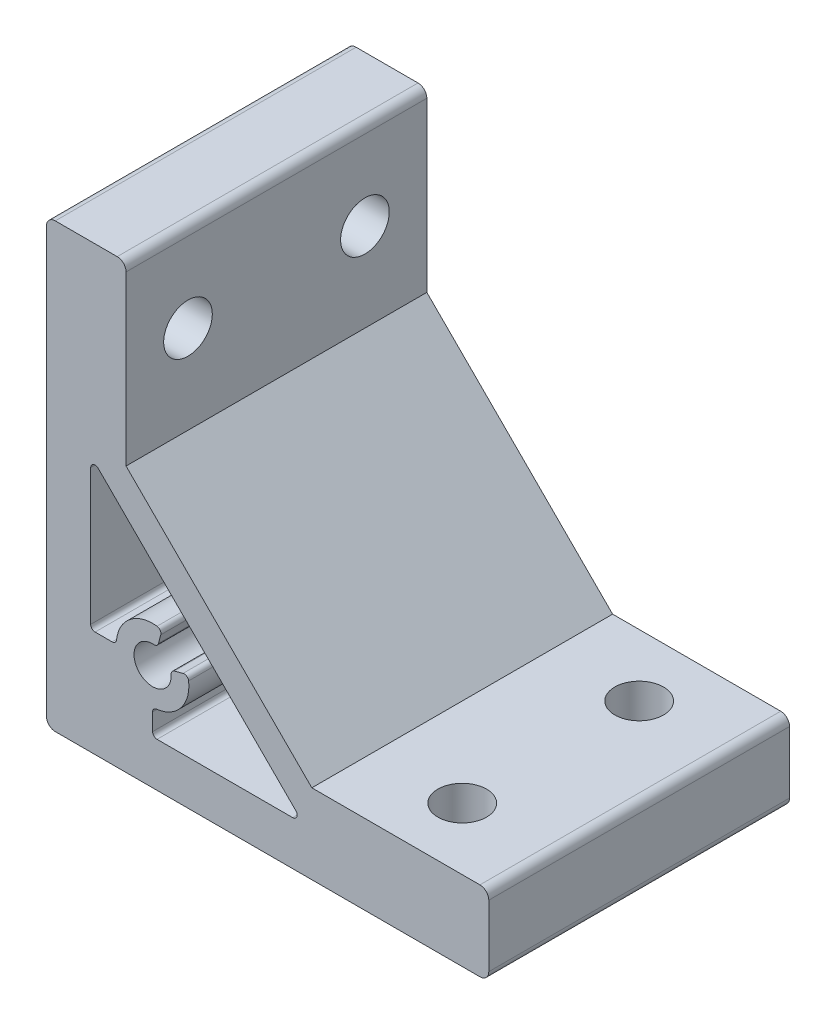
SolidWorks part; units mm, degrees
ref_plane "前视基准面" through (0, 0, 0) normal (0, 0, 1) x (1, 0, 0)
ref_plane "上视基准面" through (0, 0, 0) normal (0, 1, 0) x (1, 0, 0)
ref_plane "右视基准面" through (0, 0, 0) normal (1, 0, 0) x (0, 0, -1)
sketch "草图1" [suppressed] plane through (0, 0, 0) normal (0, 0, 1) x (1, 0, 0)
  line L12 (3, 3) -> (3, 19)
  line L13 (2, 20) -> (1, 20)
  line L14 (0, 19) -> (0, 1)
  line L15 (1, 0) -> (19, 0)
  line L16 (20, 1) -> (20, 2)
  line L17 (19, 3) -> (3, 3)
  arc A10 (3, 19) -> (2, 20) centre (2, 19) ccw
  arc A11 (1, 20) -> (0, 19) centre (1, 19) ccw
  arc A12 (0, 1) -> (1, 0) centre (1, 1) ccw
  arc A13 (19, 0) -> (20, 1) centre (19, 1) ccw
  arc A14 (20, 2) -> (19, 3) centre (19, 2) ccw
extrude "凸台-拉伸1" [suppressed] add sketch "草图1" against normal blind 14
sketch "草图2" [suppressed] plane through (0, 3, 0) normal (0, 1, 0) x (1, 0, 0)
  line L0 (19, 14) -> (3, 14) construction
  line L1 (0, 14) -> (0, 0) construction
  circle A0 centre (14, 7) radius 2.75
  dimension "D1" = 5.5
  dimension "D2" = 7
  dimension "D3" = 14
extrude "切除-拉伸1" [suppressed] cut sketch "草图2" against normal through all
sketch "草图3" [suppressed] plane through (3, 0, 0) normal (1, 0, 0) x (0, 0, -1)
  line L0 (0, 3) -> (0, 19) construction
  line L1 (14, 0) -> (0, 0) construction
  circle A0 centre (7, 14) radius 2.75
  dimension "D1" = 7
  dimension "D2" = 5.5
  dimension "D3" = 14
extrude "切除-拉伸2" [suppressed] cut sketch "草图3" against normal through all
sketch "草图4" [suppressed] plane through (0, 0, 0) normal (0, 0, 1) x (1, 0, 0)
  line L12 (3, 3) -> (3, 19)
  line L13 (2, 20) -> (1, 20)
  line L14 (0, 19) -> (0, 1)
  line L15 (1, 0) -> (19, 0)
  line L16 (20, 1) -> (20, 2)
  line L17 (19, 3) -> (3, 3)
  arc A10 (3, 19) -> (2, 20) centre (2, 19) ccw
  arc A11 (1, 20) -> (0, 19) centre (1, 19) ccw
  arc A12 (0, 1) -> (1, 0) centre (1, 1) ccw
  arc A13 (19, 0) -> (20, 1) centre (19, 1) ccw
  arc A14 (20, 2) -> (19, 3) centre (19, 2) ccw
extrude "凸台-拉伸2" [suppressed] add sketch "草图4" against normal blind 34
sketch "草图5" [suppressed] plane through (0, 3, 0) normal (0, 1, 0) x (1, 0, 0)
  line L0 (20, 17) -> (-10.7961, 17) construction
  line L1 (20, 34) -> (20, 0) construction
  line L2 (0, 34) -> (0, 0) construction
  circle A0 centre (14, 27) radius 2.75
  circle A1 centre (14, 7) radius 2.75
  dimension "D1" = 5.5
  dimension "D2" = 20
  dimension "D3" = 14
extrude "切除-拉伸3" [suppressed] cut sketch "草图5" against normal through all
sketch "草图6" [suppressed] plane through (3, 0, 0) normal (1, 0, 0) x (0, 0, -1)
  line L0 (17, 20) -> (17, -1.671) construction
  line L1 (34, 20) -> (0, 20) construction
  line L2 (34, 0) -> (0, 0) construction
  circle A0 centre (7, 14) radius 2.75
  circle A1 centre (27, 14) radius 2.75
  dimension "D1" = 5.5
  dimension "D2" = 20
  dimension "D3" = 14
extrude "切除-拉伸4" [suppressed] cut sketch "草图6" against normal through all
sketch "草图7" [suppressed] plane through (0, 0, 0) normal (0, 0, 1) x (1, 0, 0)
  line L12 (3, 3) -> (3, 19)
  line L13 (2, 20) -> (1, 20)
  line L14 (0, 19) -> (0, 1)
  line L15 (1, 0) -> (19, 0)
  line L16 (20, 1) -> (20, 2)
  line L17 (19, 3) -> (3, 3)
  arc A10 (3, 19) -> (2, 20) centre (2, 19) ccw
  arc A11 (1, 20) -> (0, 19) centre (1, 19) ccw
  arc A12 (0, 1) -> (1, 0) centre (1, 1) ccw
  arc A13 (19, 0) -> (20, 1) centre (19, 1) ccw
  arc A14 (20, 2) -> (19, 3) centre (19, 2) ccw
extrude "凸台-拉伸3" [suppressed] add sketch "草图7" against normal blind 54
sketch "草图8" [suppressed] plane through (0, 3, 0) normal (0, 1, 0) x (1, 0, 0)
  line L0 (20, 27) -> (-6.5003, 27) construction
  line L1 (20, 54) -> (20, 0) construction
  line L2 (0, 54) -> (0, 0) construction
  circle A0 centre (14, 47) radius 2.75
  circle A1 centre (14, 27) radius 2.75
  circle A2 centre (14, 7) radius 2.75
  dimension "D1" = 5.5
  dimension "D2" = 20
  dimension "D3" = 14
extrude "切除-拉伸5" [suppressed] cut sketch "草图8" against normal through all
sketch "草图9" [suppressed] plane through (3, 0, 0) normal (1, 0, 0) x (0, 0, -1)
  line L0 (27, 20) -> (27, 28.1098) construction
  line L1 (54, 20) -> (0, 20) construction
  line L2 (54, 0) -> (0, 0) construction
  circle A0 centre (7, 14) radius 2.75
  circle A1 centre (27, 14) radius 2.75
  circle A2 centre (47, 14) radius 2.75
  dimension "D1" = 5.5
  dimension "D2" = 20
  dimension "D3" = 14
extrude "切除-拉伸6" [suppressed] cut sketch "草图9" against normal through all
sketch "草图10" [suppressed] plane through (0, 0, 0) normal (0, 0, 1) x (1, 0, 0)
  line L20 (7.8119, 14.1881) -> (5, 17)
  line L21 (5, 17) -> (5, 34)
  line L22 (4, 35) -> (1, 35)
  line L23 (0, 34) -> (0, 1)
  line L24 (1, 0) -> (34, 0)
  line L25 (35, 1) -> (35, 4)
  line L26 (34, 5) -> (17, 5)
  line L27 (17, 5) -> (14.1881, 7.8119)
  line L28 (15.4436, 12.9222) -> (14.4646, 12.6602)
  line L29 (12.6602, 14.4646) -> (12.9222, 15.4436)
  arc A28 (5, 34) -> (4, 35) centre (4, 34) ccw
  arc A29 (1, 35) -> (0, 34) centre (1, 34) ccw
  arc A30 (0, 1) -> (1, 0) centre (1, 1) ccw
  arc A31 (34, 0) -> (35, 1) centre (34, 1) ccw
  arc A32 (35, 4) -> (34, 5) centre (34, 4) ccw
  arc A33 (14.265, 8.582) -> (14.1881, 7.8119) centre (14.5416, 8.1655) ccw
  arc A34 (14.265, 8.582) -> (16.069, 12.501) centre (11.9998, 11.9994) ccw
  arc A35 (16.069, 12.501) -> (15.4436, 12.9222) centre (15.5728, 12.4392) ccw
  arc A36 (14.4646, 12.6602) -> (14.095, 12.143) centre (14.5938, 12.1772) ccw
  arc A37 (12.143, 14.095) -> (14.095, 12.143) centre (11.9999, 11.9999) ccw
  arc A38 (12.143, 14.095) -> (12.6602, 14.4646) centre (12.1772, 14.5938) ccw
  arc A39 (12.9222, 15.4436) -> (12.501, 16.069) centre (12.4392, 15.5728) ccw
  arc A40 (12.501, 16.069) -> (8.582, 14.265) centre (11.9994, 11.9998) ccw
  arc A41 (7.8119, 14.1881) -> (8.582, 14.265) centre (8.1655, 14.5416) ccw
extrude "凸台-拉伸4" [suppressed] add sketch "草图10" against normal blind 14
sketch "草图11" [suppressed] plane through (0, 5, 0) normal (0, 1, 0) x (1, 0, 0)
  line L0 (34, 14) -> (17, 14) construction
  line L1 (0, 14) -> (0, 0) construction
  circle A0 centre (26, 7) radius 2.75
  dimension "D1" = 7
  dimension "D2" = 5.5
  dimension "D3" = 26
extrude "切除-拉伸7" [suppressed] cut sketch "草图11" against normal through all
sketch "草图12" [suppressed] plane through (5, 0, 0) normal (1, 0, 0) x (0, 0, -1)
  line L0 (0, 17) -> (0, 34) construction
  line L1 (14, 0) -> (0, 0) construction
  circle A0 centre (7, 26) radius 2.75
  dimension "D1" = 5.5
  dimension "D2" = 7
  dimension "D3" = 26
extrude "切除-拉伸8" [suppressed] cut sketch "草图12" against normal through all
sketch "草图13" [suppressed] plane through (0, 0, 0) normal (0, 0, 1) x (1, 0, 0)
  line L20 (7.8119, 14.1881) -> (5, 17)
  line L21 (5, 17) -> (5, 34)
  line L22 (4, 35) -> (1, 35)
  line L23 (0, 34) -> (0, 1)
  line L24 (1, 0) -> (34, 0)
  line L25 (35, 1) -> (35, 4)
  line L26 (34, 5) -> (17, 5)
  line L27 (17, 5) -> (14.1881, 7.8119)
  line L28 (15.4436, 12.9222) -> (14.4646, 12.6602)
  line L29 (12.6602, 14.4646) -> (12.9222, 15.4436)
  arc A28 (5, 34) -> (4, 35) centre (4, 34) ccw
  arc A29 (1, 35) -> (0, 34) centre (1, 34) ccw
  arc A30 (0, 1) -> (1, 0) centre (1, 1) ccw
  arc A31 (34, 0) -> (35, 1) centre (34, 1) ccw
  arc A32 (35, 4) -> (34, 5) centre (34, 4) ccw
  arc A33 (14.265, 8.582) -> (14.1881, 7.8119) centre (14.5416, 8.1655) ccw
  arc A34 (14.265, 8.582) -> (16.069, 12.501) centre (11.9998, 11.9994) ccw
  arc A35 (16.069, 12.501) -> (15.4436, 12.9222) centre (15.5728, 12.4392) ccw
  arc A36 (14.4646, 12.6602) -> (14.095, 12.143) centre (14.5938, 12.1772) ccw
  arc A37 (12.143, 14.095) -> (14.095, 12.143) centre (11.9999, 11.9999) ccw
  arc A38 (12.143, 14.095) -> (12.6602, 14.4646) centre (12.1772, 14.5938) ccw
  arc A39 (12.9222, 15.4436) -> (12.501, 16.069) centre (12.4392, 15.5728) ccw
  arc A40 (12.501, 16.069) -> (8.582, 14.265) centre (11.9994, 11.9998) ccw
  arc A41 (7.8119, 14.1881) -> (8.582, 14.265) centre (8.1655, 14.5416) ccw
extrude "凸台-拉伸5" [suppressed] add sketch "草图13" against normal blind 34
sketch "草图14" [suppressed] plane through (0, 5, 0) normal (0, 1, 0) x (1, 0, 0)
  line L0 (35, 17) -> (-9.0369, 17) construction
  line L1 (35, 34) -> (35, 0) construction
  line L2 (0, 34) -> (0, 0) construction
  circle A0 centre (26, 27) radius 2.75
  circle A1 centre (26, 7) radius 2.75
  dimension "D1" = 5.5
  dimension "D2" = 20
  dimension "D3" = 26
extrude "切除-拉伸9" [suppressed] cut sketch "草图14" against normal through all
sketch "草图15" [suppressed] plane through (5, 0, 0) normal (1, 0, 0) x (0, 0, -1)
  line L0 (17, 35) -> (17, -2.0911) construction
  line L1 (34, 35) -> (0, 35) construction
  line L2 (34, 0) -> (0, 0) construction
  circle A0 centre (7, 26) radius 2.75
  circle A1 centre (27, 26) radius 2.75
  dimension "D1" = 5.5
  dimension "D2" = 20
  dimension "D3" = 26
extrude "切除-拉伸10" [suppressed] cut sketch "草图15" against normal through all
sketch "草图16" [suppressed] plane through (0, 0, 0) normal (0, 0, 1) x (1, 0, 0)
  line L20 (7.8119, 14.1881) -> (5, 17)
  line L21 (5, 17) -> (5, 34)
  line L22 (4, 35) -> (1, 35)
  line L23 (0, 34) -> (0, 1)
  line L24 (1, 0) -> (34, 0)
  line L25 (35, 1) -> (35, 4)
  line L26 (34, 5) -> (17, 5)
  line L27 (17, 5) -> (14.1881, 7.8119)
  line L28 (15.4436, 12.9222) -> (14.4646, 12.6602)
  line L29 (12.6602, 14.4646) -> (12.9222, 15.4436)
  arc A28 (5, 34) -> (4, 35) centre (4, 34) ccw
  arc A29 (1, 35) -> (0, 34) centre (1, 34) ccw
  arc A30 (0, 1) -> (1, 0) centre (1, 1) ccw
  arc A31 (34, 0) -> (35, 1) centre (34, 1) ccw
  arc A32 (35, 4) -> (34, 5) centre (34, 4) ccw
  arc A33 (14.265, 8.582) -> (14.1881, 7.8119) centre (14.5416, 8.1655) ccw
  arc A34 (14.265, 8.582) -> (16.069, 12.501) centre (11.9998, 11.9994) ccw
  arc A35 (16.069, 12.501) -> (15.4436, 12.9222) centre (15.5728, 12.4392) ccw
  arc A36 (14.4646, 12.6602) -> (14.095, 12.143) centre (14.5938, 12.1772) ccw
  arc A37 (12.143, 14.095) -> (14.095, 12.143) centre (11.9999, 11.9999) ccw
  arc A38 (12.143, 14.095) -> (12.6602, 14.4646) centre (12.1772, 14.5938) ccw
  arc A39 (12.9222, 15.4436) -> (12.501, 16.069) centre (12.4392, 15.5728) ccw
  arc A40 (12.501, 16.069) -> (8.582, 14.265) centre (11.9994, 11.9998) ccw
  arc A41 (7.8119, 14.1881) -> (8.582, 14.265) centre (8.1655, 14.5416) ccw
extrude "凸台-拉伸6" [suppressed] add sketch "草图16" against normal blind 54
sketch "草图17" [suppressed] plane through (0, 5, 0) normal (0, 1, 0) x (1, 0, 0)
  line L0 (35, 27) -> (46.9961, 27) construction
  line L1 (35, 54) -> (35, 0) construction
  line L2 (0, 54) -> (0, 0) construction
  circle A0 centre (26, 47) radius 2.75
  circle A1 centre (26, 27) radius 2.75
  circle A2 centre (26, 7) radius 2.75
  dimension "D1" = 5.5
  dimension "D2" = 20
  dimension "D3" = 26
extrude "切除-拉伸11" [suppressed] cut sketch "草图17" against normal through all
sketch "草图18" [suppressed] plane through (5, 0, 0) normal (1, 0, 0) x (0, 0, -1)
  line L0 (27, 35) -> (27, 41.3305) construction
  line L1 (54, 35) -> (0, 35) construction
  line L2 (54, 0) -> (0, 0) construction
  circle A0 centre (7, 26) radius 2.75
  circle A1 centre (27, 26) radius 2.75
  circle A2 centre (47, 26) radius 2.75
  dimension "D1" = 5.5
  dimension "D2" = 20
  dimension "D3" = 26
extrude "切除-拉伸12" [suppressed] cut sketch "草图18" against normal through all
sketch "草图19" [suppressed] plane through (0, 0, 0) normal (0, 0, 1) x (1, 0, 0)
  line L16 (-14.794, 9) -> (-54, 9)
  line L17 (-55, 8) -> (-55, 1)
  line L18 (-54, 0) -> (-1, 0)
  line L19 (0, 1) -> (0, 54)
  line L20 (-1, 55) -> (-8, 55)
  line L21 (-9, 54) -> (-9, 14.795)
  line L22 (-12.9219, 15.4435) -> (-12.6599, 14.4646)
  line L23 (-14.4641, 12.66) -> (-15.443, 12.923)
  arc A24 (-15.443, 12.923) -> (-16.069, 12.501) centre (-15.5727, 12.4401) ccw
  arc A25 (-16.069, 12.501) -> (-14.794, 9) centre (-11.9997, 12.0003) ccw
  arc A26 (-54, 9) -> (-55, 8) centre (-54, 8) ccw
  arc A27 (-55, 1) -> (-54, 0) centre (-54, 1) ccw
  arc A28 (-1, 0) -> (0, 1) centre (-1, 1) ccw
  arc A29 (0, 54) -> (-1, 55) centre (-1, 54) ccw
  arc A30 (-8, 55) -> (-9, 54) centre (-8, 54) ccw
  arc A31 (-9, 14.795) -> (-12.5, 16.069) centre (-11.9994, 11.9997) ccw
  arc A32 (-12.5, 16.069) -> (-12.9219, 15.4435) centre (-12.4389, 15.5728) ccw
  arc A33 (-12.6599, 14.4646) -> (-12.143, 14.095) centre (-12.1769, 14.5939) ccw
  arc A34 (-14.095, 12.143) -> (-12.143, 14.095) centre (-11.9999, 11.9999) ccw
  arc A35 (-14.095, 12.143) -> (-14.4641, 12.66) centre (-14.5938, 12.1772) ccw
extrude "凸台-拉伸7" [suppressed] add sketch "草图19" against normal blind 14
sketch "草图20" [suppressed] plane through (-9, 0, 0) normal (-1, 0, 0) x (0, 0, 1)
  line L0 (-14, 54) -> (-14, 14.795) construction
  line L1 (-14, 0) -> (0, 0) construction
  circle A0 centre (-7, 25) radius 2.75
  circle A1 centre (-7, 45) radius 2.75
  dimension "D1" = 5.5
  dimension "D2" = 7
  dimension "D3" = 25
  dimension "D4" = 45
extrude "切除-拉伸13" [suppressed] cut sketch "草图20" against normal through all
sketch "草图21" [suppressed] plane through (0, 9, 0) normal (0, 1, 0) x (1, 0, 0)
  line L0 (-14.794, 0) -> (-54, 0) construction
  line L1 (0, 14) -> (0, 0) construction
  circle A0 centre (-45, 7) radius 2.75
  circle A1 centre (-25, 7) radius 2.75
  dimension "D1" = 5.5
  dimension "D2" = 7
  dimension "D3" = 25
  dimension "D4" = 45
extrude "切除-拉伸14" [suppressed] cut sketch "草图21" against normal through all
sketch "草图22" [suppressed] plane through (0, 0, 0) normal (0, 0, 1) x (1, 0, 0)
  line L16 (-14.794, 9) -> (-54, 9)
  line L17 (-55, 8) -> (-55, 1)
  line L18 (-54, 0) -> (-1, 0)
  line L19 (0, 1) -> (0, 54)
  line L20 (-1, 55) -> (-8, 55)
  line L21 (-9, 54) -> (-9, 14.795)
  line L22 (-12.9219, 15.4435) -> (-12.6599, 14.4646)
  line L23 (-14.4641, 12.66) -> (-15.443, 12.923)
  arc A24 (-15.443, 12.923) -> (-16.069, 12.501) centre (-15.5727, 12.4401) ccw
  arc A25 (-16.069, 12.501) -> (-14.794, 9) centre (-11.9997, 12.0003) ccw
  arc A26 (-54, 9) -> (-55, 8) centre (-54, 8) ccw
  arc A27 (-55, 1) -> (-54, 0) centre (-54, 1) ccw
  arc A28 (-1, 0) -> (0, 1) centre (-1, 1) ccw
  arc A29 (0, 54) -> (-1, 55) centre (-1, 54) ccw
  arc A30 (-8, 55) -> (-9, 54) centre (-8, 54) ccw
  arc A31 (-9, 14.795) -> (-12.5, 16.069) centre (-11.9994, 11.9997) ccw
  arc A32 (-12.5, 16.069) -> (-12.9219, 15.4435) centre (-12.4389, 15.5728) ccw
  arc A33 (-12.6599, 14.4646) -> (-12.143, 14.095) centre (-12.1769, 14.5939) ccw
  arc A34 (-14.095, 12.143) -> (-12.143, 14.095) centre (-11.9999, 11.9999) ccw
  arc A35 (-14.095, 12.143) -> (-14.4641, 12.66) centre (-14.5938, 12.1772) ccw
extrude "凸台-拉伸8" [suppressed] add sketch "草图22" against normal blind 34
sketch "草图23" [suppressed] plane through (-9, 0, 0) normal (-1, 0, 0) x (0, 0, 1)
  line L0 (-17, 55) -> (-17, 18.2791) construction
  line L1 (-34, 55) -> (0, 55) construction
  line L2 (-34, 0) -> (0, 0) construction
  circle A0 centre (-27, 45) radius 2.75
  circle A1 centre (-7, 45) radius 2.75
  circle A2 centre (-27, 25) radius 2.75
  circle A3 centre (-7, 25) radius 2.75
  dimension "D1" = 5.5
  dimension "D2" = 20
  dimension "D3" = 25
  dimension "D4" = 45
extrude "切除-拉伸15" [suppressed] cut sketch "草图23" against normal through all
sketch "草图24" [suppressed] plane through (0, 9, 0) normal (0, 1, 0) x (1, 0, 0)
  line L0 (-55, 17) -> (-20.4322, 17) construction
  line L1 (-55, 34) -> (-55, 0) construction
  line L2 (0, 34) -> (0, 0) construction
  circle A0 centre (-45, 27) radius 2.75
  circle A1 centre (-25, 27) radius 2.75
  circle A2 centre (-45, 7) radius 2.75
  circle A3 centre (-25, 7) radius 2.75
  dimension "D1" = 5.5
  dimension "D2" = 20
  dimension "D3" = 25
  dimension "D4" = 45
extrude "切除-拉伸16" [suppressed] cut sketch "草图24" against normal through all
sketch "草图25" [suppressed] plane through (0, 0, 0) normal (0, 0, 1) x (1, 0, 0)
  line L16 (-14.794, 9) -> (-54, 9)
  line L17 (-55, 8) -> (-55, 1)
  line L18 (-54, 0) -> (-1, 0)
  line L19 (0, 1) -> (0, 54)
  line L20 (-1, 55) -> (-8, 55)
  line L21 (-9, 54) -> (-9, 14.795)
  line L22 (-12.9219, 15.4435) -> (-12.6599, 14.4646)
  line L23 (-14.4641, 12.66) -> (-15.443, 12.923)
  arc A24 (-15.443, 12.923) -> (-16.069, 12.501) centre (-15.5727, 12.4401) ccw
  arc A25 (-16.069, 12.501) -> (-14.794, 9) centre (-11.9997, 12.0003) ccw
  arc A26 (-54, 9) -> (-55, 8) centre (-54, 8) ccw
  arc A27 (-55, 1) -> (-54, 0) centre (-54, 1) ccw
  arc A28 (-1, 0) -> (0, 1) centre (-1, 1) ccw
  arc A29 (0, 54) -> (-1, 55) centre (-1, 54) ccw
  arc A30 (-8, 55) -> (-9, 54) centre (-8, 54) ccw
  arc A31 (-9, 14.795) -> (-12.5, 16.069) centre (-11.9994, 11.9997) ccw
  arc A32 (-12.5, 16.069) -> (-12.9219, 15.4435) centre (-12.4389, 15.5728) ccw
  arc A33 (-12.6599, 14.4646) -> (-12.143, 14.095) centre (-12.1769, 14.5939) ccw
  arc A34 (-14.095, 12.143) -> (-12.143, 14.095) centre (-11.9999, 11.9999) ccw
  arc A35 (-14.095, 12.143) -> (-14.4641, 12.66) centre (-14.5938, 12.1772) ccw
extrude "凸台-拉伸9" [suppressed] add sketch "草图25" against normal blind 54
sketch "草图26" [suppressed] plane through (-9, 0, 0) normal (-1, 0, 0) x (0, 0, 1)
  line L0 (-27, 55) -> (-27, 17.8329) construction
  line L1 (-54, 55) -> (0, 55) construction
  line L2 (-54, 0) -> (0, 0) construction
  circle A0 centre (-47, 45) radius 2.75
  circle A1 centre (-27, 45) radius 2.75
  circle A2 centre (-7, 45) radius 2.75
  circle A3 centre (-7, 25) radius 2.75
  circle A4 centre (-27, 25) radius 2.75
  circle A5 centre (-47, 25) radius 2.75
  dimension "D1" = 5.5
  dimension "D2" = 20
  dimension "D3" = 25
  dimension "D4" = 45
extrude "切除-拉伸17" [suppressed] cut sketch "草图26" against normal through all
sketch "草图27" [suppressed] plane through (0, 9, 0) normal (0, 1, 0) x (1, 0, 0)
  line L0 (-55, 27) -> (-66.2684, 27) construction
  line L1 (-55, 54) -> (-55, 0) construction
  line L2 (0, 54) -> (0, 0) construction
  circle A0 centre (-45, 47) radius 2.75
  circle A1 centre (-25, 47) radius 2.75
  circle A2 centre (-45, 27) radius 2.75
  circle A3 centre (-25, 27) radius 2.75
  circle A4 centre (-45, 7) radius 2.75
  circle A5 centre (-25, 7) radius 2.75
  dimension "D1" = 5.5
  dimension "D2" = 20
  dimension "D3" = 25
  dimension "D4" = 45
extrude "切除-拉伸18" [suppressed] cut sketch "草图27" against normal through all
sketch "草图28" [suppressed] plane through (0, 0, 0) normal (0, 0, 1) x (1, 0, 0)
  line L14 (9, 30) -> (9, 49)
  line L15 (8, 50) -> (1, 50)
  line L16 (0, 49) -> (0, 1)
  line L17 (1, 0) -> (49, 0)
  line L18 (50, 1) -> (50, 8)
  line L19 (49, 9) -> (30, 9)
  line L20 (30, 9) -> (9, 30)
  line L28 (5.5, 12) -> (7.428, 12)
  line L29 (5, 27.8439) -> (5, 12.5)
  line L30 (28.1965, 5.8535) -> (5.8536, 28.1974)
  line L31 (12.5, 5) -> (27.8429, 5)
  line L32 (12, 7.4269) -> (12, 5.5)
  line L33 (14.4641, 12.6598) -> (15.444, 12.923)
  line L34 (12.9231, 15.4435) -> (12.6612, 14.4646)
  arc A10 (9, 49) -> (8, 50) centre (8, 49) ccw
  arc A11 (1, 50) -> (0, 49) centre (1, 49) ccw
  arc A12 (0, 1) -> (1, 0) centre (1, 1) ccw
  arc A13 (49, 0) -> (50, 1) centre (49, 1) ccw
  arc A14 (50, 8) -> (49, 9) centre (49, 8) ccw
  arc A36 (7.428, 12) -> (7.925, 12.445) centre (7.428, 12.5) ccw
  arc A37 (5, 12.5) -> (5.5, 12) centre (5.5, 12.5) ccw
  arc A38 (5.8536, 28.1974) -> (5, 27.8439) centre (5.5, 27.8439) ccw
  arc A39 (27.8429, 5) -> (28.1965, 5.8535) centre (27.8429, 5.5) ccw
  arc A40 (12, 5.5) -> (12.5, 5) centre (12.5, 5.5) ccw
  arc A41 (12.446, 7.924) -> (12, 7.4269) centre (12.5, 7.4269) ccw
  arc A42 (12.446, 7.924) -> (16.07, 12.501) centre (12.0008, 11.9998) ccw
  arc A43 (16.07, 12.501) -> (15.444, 12.923) centre (15.5737, 12.4401) ccw
  arc A44 (14.4641, 12.6598) -> (14.095, 12.143) centre (14.5939, 12.1769) ccw
  arc A45 (12.144, 14.095) -> (14.095, 12.143) centre (11.9999, 12) ccw
  arc A46 (12.144, 14.095) -> (12.6612, 14.4646) centre (12.1782, 14.5938) ccw
  arc A47 (12.9231, 15.4435) -> (12.501, 16.069) centre (12.4401, 15.5727) ccw
  arc A48 (12.501, 16.069) -> (7.925, 12.445) centre (12.0007, 11.9996) ccw
extrude "凸台-拉伸10" [suppressed] add sketch "草图28" along normal blind 14
sketch "草图29" [suppressed] plane through (9, 0, 0) normal (1, 0, 0) x (0, 0, -1)
  line L0 (-14, 30) -> (-14, 49) construction
  line L1 (-14, 0) -> (0, 0) construction
  circle A0 centre (-7, 40) radius 2.75
  dimension "D1" = 7
  dimension "D2" = 5.5
  dimension "D3" = 40
extrude "切除-拉伸19" [suppressed] cut sketch "草图29" against normal through all
sketch "草图30" [suppressed] plane through (0, 9, 0) normal (0, 1, 0) x (1, 0, 0)
  line L0 (49, 0) -> (30, 0) construction
  line L1 (0, -14) -> (0, 0) construction
  circle A0 centre (40, -7) radius 2.75
  dimension "D1" = 5.5
  dimension "D2" = 7
  dimension "D3" = 40
extrude "切除-拉伸20" [suppressed] cut sketch "草图30" against normal through all
sketch "草图31" plane through (0, 0, 0) normal (0, 0, 1) x (1, 0, 0)
  line L14 (9, 30) -> (9, 49)
  line L15 (8, 50) -> (1, 50)
  line L16 (0, 49) -> (0, 1)
  line L17 (1, 0) -> (49, 0)
  line L18 (50, 1) -> (50, 8)
  line L19 (49, 9) -> (30, 9)
  line L20 (30, 9) -> (9, 30)
  line L28 (5.5, 12) -> (7.428, 12)
  line L29 (5, 27.8439) -> (5, 12.5)
  line L30 (28.1965, 5.8535) -> (5.8536, 28.1974)
  line L31 (12.5, 5) -> (27.8429, 5)
  line L32 (12, 7.4269) -> (12, 5.5)
  line L33 (14.4641, 12.6598) -> (15.444, 12.923)
  line L34 (12.9231, 15.4435) -> (12.6612, 14.4646)
  arc A10 (9, 49) -> (8, 50) centre (8, 49) ccw
  arc A11 (1, 50) -> (0, 49) centre (1, 49) ccw
  arc A12 (0, 1) -> (1, 0) centre (1, 1) ccw
  arc A13 (49, 0) -> (50, 1) centre (49, 1) ccw
  arc A14 (50, 8) -> (49, 9) centre (49, 8) ccw
  arc A36 (7.428, 12) -> (7.925, 12.445) centre (7.428, 12.5) ccw
  arc A37 (5, 12.5) -> (5.5, 12) centre (5.5, 12.5) ccw
  arc A38 (5.8536, 28.1974) -> (5, 27.8439) centre (5.5, 27.8439) ccw
  arc A39 (27.8429, 5) -> (28.1965, 5.8535) centre (27.8429, 5.5) ccw
  arc A40 (12, 5.5) -> (12.5, 5) centre (12.5, 5.5) ccw
  arc A41 (12.446, 7.924) -> (12, 7.4269) centre (12.5, 7.4269) ccw
  arc A42 (12.446, 7.924) -> (16.07, 12.501) centre (12.0008, 11.9998) ccw
  arc A43 (16.07, 12.501) -> (15.444, 12.923) centre (15.5737, 12.4401) ccw
  arc A44 (14.4641, 12.6598) -> (14.095, 12.143) centre (14.5939, 12.1769) ccw
  arc A45 (12.144, 14.095) -> (14.095, 12.143) centre (11.9999, 12) ccw
  arc A46 (12.144, 14.095) -> (12.6612, 14.4646) centre (12.1782, 14.5938) ccw
  arc A47 (12.9231, 15.4435) -> (12.501, 16.069) centre (12.4401, 15.5727) ccw
  arc A48 (12.501, 16.069) -> (7.925, 12.445) centre (12.0007, 11.9996) ccw
extrude "凸台-拉伸11" add sketch "草图31" against normal blind 34
sketch "草图32" plane through (0, 9, 0) normal (0, 1, 0) x (1, 0, 0)
  line L0 (50, 17) -> (60.62, 17) construction
  line L1 (50, 34) -> (50, 0) construction
  line L2 (0, 34) -> (0, 0) construction
  circle A0 centre (40, 27) radius 2.75
  circle A1 centre (40, 7) radius 2.75
  dimension "D1" = 5.5
  dimension "D2" = 20
  dimension "D3" = 40
extrude "切除-拉伸21" cut sketch "草图32" against normal through all
sketch "草图33" plane through (9, 0, 0) normal (1, 0, 0) x (0, 0, -1)
  line L0 (17, 50) -> (17, 18.713) construction
  line L1 (34, 50) -> (0, 50) construction
  line L2 (34, 0) -> (0, 0) construction
  circle A0 centre (7, 40) radius 2.75
  circle A1 centre (27, 40) radius 2.75
  dimension "D1" = 5.5
  dimension "D2" = 20
  dimension "D3" = 40
extrude "切除-拉伸22" cut sketch "草图33" against normal through all
sketch "草图34" [suppressed] plane through (0, 0, 0) normal (0, 0, 1) x (1, 0, 0)
  line L14 (9, 30) -> (9, 49)
  line L15 (8, 50) -> (1, 50)
  line L16 (0, 49) -> (0, 1)
  line L17 (1, 0) -> (49, 0)
  line L18 (50, 1) -> (50, 8)
  line L19 (49, 9) -> (30, 9)
  line L20 (30, 9) -> (9, 30)
  line L28 (5.5, 12) -> (7.428, 12)
  line L29 (5, 27.8439) -> (5, 12.5)
  line L30 (28.1965, 5.8535) -> (5.8536, 28.1974)
  line L31 (12.5, 5) -> (27.8429, 5)
  line L32 (12, 7.4269) -> (12, 5.5)
  line L33 (14.4641, 12.6598) -> (15.444, 12.923)
  line L34 (12.9231, 15.4435) -> (12.6612, 14.4646)
  arc A10 (9, 49) -> (8, 50) centre (8, 49) ccw
  arc A11 (1, 50) -> (0, 49) centre (1, 49) ccw
  arc A12 (0, 1) -> (1, 0) centre (1, 1) ccw
  arc A13 (49, 0) -> (50, 1) centre (49, 1) ccw
  arc A14 (50, 8) -> (49, 9) centre (49, 8) ccw
  arc A36 (7.428, 12) -> (7.925, 12.445) centre (7.428, 12.5) ccw
  arc A37 (5, 12.5) -> (5.5, 12) centre (5.5, 12.5) ccw
  arc A38 (5.8536, 28.1974) -> (5, 27.8439) centre (5.5, 27.8439) ccw
  arc A39 (27.8429, 5) -> (28.1965, 5.8535) centre (27.8429, 5.5) ccw
  arc A40 (12, 5.5) -> (12.5, 5) centre (12.5, 5.5) ccw
  arc A41 (12.446, 7.924) -> (12, 7.4269) centre (12.5, 7.4269) ccw
  arc A42 (12.446, 7.924) -> (16.07, 12.501) centre (12.0008, 11.9998) ccw
  arc A43 (16.07, 12.501) -> (15.444, 12.923) centre (15.5737, 12.4401) ccw
  arc A44 (14.4641, 12.6598) -> (14.095, 12.143) centre (14.5939, 12.1769) ccw
  arc A45 (12.144, 14.095) -> (14.095, 12.143) centre (11.9999, 12) ccw
  arc A46 (12.144, 14.095) -> (12.6612, 14.4646) centre (12.1782, 14.5938) ccw
  arc A47 (12.9231, 15.4435) -> (12.501, 16.069) centre (12.4401, 15.5727) ccw
  arc A48 (12.501, 16.069) -> (7.925, 12.445) centre (12.0007, 11.9996) ccw
extrude "凸台-拉伸12" [suppressed] add sketch "草图34" against normal blind 54
sketch "草图35" [suppressed] plane through (0, 9, 0) normal (0, 1, 0) x (1, 0, 0)
  line L0 (50, 27) -> (60.775, 27) construction
  line L1 (50, 54) -> (50, 0) construction
  line L2 (0, 54) -> (0, 0) construction
  circle A0 centre (40, 47) radius 2.75
  circle A1 centre (40, 27) radius 2.75
  circle A2 centre (40, 7) radius 2.75
  dimension "D1" = 5.5
  dimension "D2" = 20
  dimension "D3" = 40
extrude "切除-拉伸23" [suppressed] cut sketch "草图35" against normal through all
sketch "草图36" [suppressed] plane through (9, 0, 0) normal (1, 0, 0) x (0, 0, -1)
  line L0 (27, 50) -> (27, 56.3689) construction
  line L1 (54, 50) -> (0, 50) construction
  line L2 (54, 0) -> (0, 0) construction
  circle A0 centre (7, 40) radius 2.75
  circle A1 centre (27, 40) radius 2.75
  circle A2 centre (47, 40) radius 2.75
  dimension "D1" = 5.5
  dimension "D2" = 20
  dimension "D3" = 40
extrude "切除-拉伸24" [suppressed] cut sketch "草图36" against normal through all
sketch "草图37" [suppressed] plane through (0, 0, 0) normal (0, 0, 1) x (1, 0, 0)
  line L14 (40, 9) -> (9, 40)
  line L15 (9, 40) -> (9, 59)
  line L16 (8, 60) -> (1, 60)
  line L17 (0, 59) -> (0, 1)
  line L18 (1, 0) -> (59, 0)
  line L19 (60, 1) -> (60, 8)
  line L20 (59, 9) -> (40, 9)
  line L28 (6, 12) -> (7.428, 12)
  line L29 (5, 37.8429) -> (5, 13)
  line L30 (38.1964, 5.8536) -> (5.8536, 38.1964)
  line L31 (12.5, 5) -> (37.844, 5)
  line L32 (12, 7.4269) -> (12, 5.5)
  line L33 (14.4656, 12.6602) -> (15.4446, 12.9222)
  line L34 (12.9231, 15.4435) -> (12.6612, 14.4646)
  arc A10 (9, 59) -> (8, 60) centre (8, 59) ccw
  arc A11 (1, 60) -> (0, 59) centre (1, 59) ccw
  arc A12 (0, 1) -> (1, 0) centre (1, 1) ccw
  arc A13 (59, 0) -> (60, 1) centre (59, 1) ccw
  arc A14 (60, 8) -> (59, 9) centre (59, 8) ccw
  arc A36 (12.501, 16.069) -> (7.925, 12.445) centre (12.0007, 11.9996) ccw
  arc A37 (7.428, 12) -> (7.925, 12.445) centre (7.428, 12.5) ccw
  arc A38 (5, 13) -> (6, 12) centre (6, 13) ccw
  arc A39 (5.8536, 38.1964) -> (5, 37.8429) centre (5.5, 37.8429) ccw
  arc A40 (37.844, 5) -> (38.1964, 5.8536) centre (37.8429, 5.5) ccw
  arc A41 (12, 5.5) -> (12.5, 5) centre (12.5, 5.5) ccw
  arc A42 (12.446, 7.924) -> (12, 7.4269) centre (12.5, 7.4269) ccw
  arc A43 (12.446, 7.924) -> (16.07, 12.501) centre (12.0008, 11.9998) ccw
  arc A44 (16.07, 12.501) -> (15.4446, 12.9222) centre (15.5738, 12.4392) ccw
  arc A45 (14.4656, 12.6602) -> (14.096, 12.143) centre (14.5948, 12.1772) ccw
  arc A46 (12.144, 14.095) -> (14.096, 12.143) centre (12.0009, 11.9999) ccw
  arc A47 (12.144, 14.095) -> (12.6612, 14.4646) centre (12.1782, 14.5938) ccw
  arc A48 (12.9231, 15.4435) -> (12.501, 16.069) centre (12.4401, 15.5727) ccw
extrude "凸台-拉伸13" [suppressed] add sketch "草图37" against normal blind 14
sketch "草图38" [suppressed] plane through (0, 9, 0) normal (0, 1, 0) x (1, 0, 0)
  line L0 (59, 14) -> (40, 14) construction
  line L1 (0, 14) -> (0, 0) construction
  circle A0 centre (50, 7) radius 2.75
  dimension "D1" = 5.5
  dimension "D2" = 7
  dimension "D3" = 50
extrude "切除-拉伸25" [suppressed] cut sketch "草图38" against normal through all
sketch "草图39" [suppressed] plane through (9, 0, 0) normal (1, 0, 0) x (0, 0, -1)
  line L0 (0, 40) -> (0, 59) construction
  line L1 (14, 0) -> (0, 0) construction
  circle A0 centre (7, 50) radius 2.75
  dimension "D1" = 5.5
  dimension "D2" = 7
  dimension "D3" = 50
extrude "切除-拉伸26" [suppressed] cut sketch "草图39" against normal through all
sketch "草图40" [suppressed] plane through (0, 0, 0) normal (0, 0, 1) x (1, 0, 0)
  line L14 (40, 9) -> (9, 40)
  line L15 (9, 40) -> (9, 59)
  line L16 (8, 60) -> (1, 60)
  line L17 (0, 59) -> (0, 1)
  line L18 (1, 0) -> (59, 0)
  line L19 (60, 1) -> (60, 8)
  line L20 (59, 9) -> (40, 9)
  line L28 (6, 12) -> (7.428, 12)
  line L29 (5, 37.8429) -> (5, 13)
  line L30 (38.1964, 5.8536) -> (5.8536, 38.1964)
  line L31 (12.5, 5) -> (37.844, 5)
  line L32 (12, 7.4269) -> (12, 5.5)
  line L33 (14.4656, 12.6602) -> (15.4446, 12.9222)
  line L34 (12.9231, 15.4435) -> (12.6612, 14.4646)
  arc A10 (9, 59) -> (8, 60) centre (8, 59) ccw
  arc A11 (1, 60) -> (0, 59) centre (1, 59) ccw
  arc A12 (0, 1) -> (1, 0) centre (1, 1) ccw
  arc A13 (59, 0) -> (60, 1) centre (59, 1) ccw
  arc A14 (60, 8) -> (59, 9) centre (59, 8) ccw
  arc A36 (12.501, 16.069) -> (7.925, 12.445) centre (12.0007, 11.9996) ccw
  arc A37 (7.428, 12) -> (7.925, 12.445) centre (7.428, 12.5) ccw
  arc A38 (5, 13) -> (6, 12) centre (6, 13) ccw
  arc A39 (5.8536, 38.1964) -> (5, 37.8429) centre (5.5, 37.8429) ccw
  arc A40 (37.844, 5) -> (38.1964, 5.8536) centre (37.8429, 5.5) ccw
  arc A41 (12, 5.5) -> (12.5, 5) centre (12.5, 5.5) ccw
  arc A42 (12.446, 7.924) -> (12, 7.4269) centre (12.5, 7.4269) ccw
  arc A43 (12.446, 7.924) -> (16.07, 12.501) centre (12.0008, 11.9998) ccw
  arc A44 (16.07, 12.501) -> (15.4446, 12.9222) centre (15.5738, 12.4392) ccw
  arc A45 (14.4656, 12.6602) -> (14.096, 12.143) centre (14.5948, 12.1772) ccw
  arc A46 (12.144, 14.095) -> (14.096, 12.143) centre (12.0009, 11.9999) ccw
  arc A47 (12.144, 14.095) -> (12.6612, 14.4646) centre (12.1782, 14.5938) ccw
  arc A48 (12.9231, 15.4435) -> (12.501, 16.069) centre (12.4401, 15.5727) ccw
extrude "凸台-拉伸14" [suppressed] add sketch "草图40" against normal blind 34
sketch "草图41" [suppressed] plane through (0, 9, 0) normal (0, 1, 0) x (1, 0, 0)
  line L0 (60, 17) -> (42.7252, 17) construction
  line L1 (60, 34) -> (60, 0) construction
  line L2 (0, 34) -> (0, 0) construction
  circle A0 centre (50, 27) radius 2.75
  circle A1 centre (50, 7) radius 2.75
  dimension "D1" = 5.5
  dimension "D2" = 20
  dimension "D3" = 50
extrude "切除-拉伸27" [suppressed] cut sketch "草图41" against normal through all
sketch "草图42" [suppressed] plane through (9, 0, 0) normal (1, 0, 0) x (0, 0, -1)
  line L0 (17, 60) -> (17, 43.1418) construction
  line L1 (34, 60) -> (0, 60) construction
  line L2 (34, 0) -> (0, 0) construction
  circle A0 centre (7, 50) radius 2.75
  circle A1 centre (27, 50) radius 2.75
  dimension "D1" = 5.5
  dimension "D2" = 50
  dimension "D3" = 20
extrude "切除-拉伸28" [suppressed] cut sketch "草图42" against normal through all
sketch "草图43" [suppressed] plane through (0, 0, 0) normal (0, 0, 1) x (1, 0, 0)
  line L14 (40, 9) -> (9, 40)
  line L15 (9, 40) -> (9, 59)
  line L16 (8, 60) -> (1, 60)
  line L17 (0, 59) -> (0, 1)
  line L18 (1, 0) -> (59, 0)
  line L19 (60, 1) -> (60, 8)
  line L20 (59, 9) -> (40, 9)
  line L28 (6, 12) -> (7.428, 12)
  line L29 (5, 37.8429) -> (5, 13)
  line L30 (38.1964, 5.8536) -> (5.8536, 38.1964)
  line L31 (12.5, 5) -> (37.844, 5)
  line L32 (12, 7.4269) -> (12, 5.5)
  line L33 (14.4656, 12.6602) -> (15.4446, 12.9222)
  line L34 (12.9231, 15.4435) -> (12.6612, 14.4646)
  arc A10 (9, 59) -> (8, 60) centre (8, 59) ccw
  arc A11 (1, 60) -> (0, 59) centre (1, 59) ccw
  arc A12 (0, 1) -> (1, 0) centre (1, 1) ccw
  arc A13 (59, 0) -> (60, 1) centre (59, 1) ccw
  arc A14 (60, 8) -> (59, 9) centre (59, 8) ccw
  arc A36 (12.501, 16.069) -> (7.925, 12.445) centre (12.0007, 11.9996) ccw
  arc A37 (7.428, 12) -> (7.925, 12.445) centre (7.428, 12.5) ccw
  arc A38 (5, 13) -> (6, 12) centre (6, 13) ccw
  arc A39 (5.8536, 38.1964) -> (5, 37.8429) centre (5.5, 37.8429) ccw
  arc A40 (37.844, 5) -> (38.1964, 5.8536) centre (37.8429, 5.5) ccw
  arc A41 (12, 5.5) -> (12.5, 5) centre (12.5, 5.5) ccw
  arc A42 (12.446, 7.924) -> (12, 7.4269) centre (12.5, 7.4269) ccw
  arc A43 (12.446, 7.924) -> (16.07, 12.501) centre (12.0008, 11.9998) ccw
  arc A44 (16.07, 12.501) -> (15.4446, 12.9222) centre (15.5738, 12.4392) ccw
  arc A45 (14.4656, 12.6602) -> (14.096, 12.143) centre (14.5948, 12.1772) ccw
  arc A46 (12.144, 14.095) -> (14.096, 12.143) centre (12.0009, 11.9999) ccw
  arc A47 (12.144, 14.095) -> (12.6612, 14.4646) centre (12.1782, 14.5938) ccw
  arc A48 (12.9231, 15.4435) -> (12.501, 16.069) centre (12.4401, 15.5727) ccw
extrude "凸台-拉伸15" [suppressed] add sketch "草图43" against normal blind 54
sketch "草图44" [suppressed] plane through (0, 9, 0) normal (0, 1, 0) x (1, 0, 0)
  line L0 (60, 27) -> (67.8923, 27) construction
  line L1 (60, 54) -> (60, 0) construction
  line L2 (0, 54) -> (0, 0) construction
  circle A0 centre (50, 47) radius 2.75
  circle A1 centre (50, 27) radius 2.75
  circle A2 centre (50, 7) radius 2.75
  dimension "D1" = 5.5
  dimension "D2" = 20
  dimension "D3" = 50
extrude "切除-拉伸29" [suppressed] cut sketch "草图44" against normal through all
sketch "草图45" [suppressed] plane through (9, 0, 0) normal (1, 0, 0) x (0, 0, -1)
  line L0 (27, 60) -> (27, 66.2617) construction
  line L1 (54, 60) -> (0, 60) construction
  line L2 (54, 0) -> (0, 0) construction
  circle A0 centre (7, 50) radius 2.75
  circle A1 centre (27, 50) radius 2.75
  circle A2 centre (47, 50) radius 2.75
  dimension "D1" = 5.5
  dimension "D2" = 20
  dimension "D3" = 50
extrude "切除-拉伸30" [suppressed] cut sketch "草图45" against normal through all
sketch "草图46" [suppressed] plane through (0, 0, 0) normal (0, 0, 1) x (1, 0, 0)
  line L14 (47.8087, 36.829) -> (61.2436, 50.2639)
  line L15 (61.2436, 51.6781) -> (56.2938, 56.6279)
  line L16 (54.8796, 56.6279) -> (0.4329, 2.1812)
  line L17 (1.8471, -1.233) -> (78.8467, -1.233)
  line L18 (79.8467, -0.233) -> (79.8467, 6.767)
  line L19 (78.8467, 7.767) -> (59.8467, 7.767)
  line L20 (59.8467, 7.767) -> (47.8087, 36.829)
  line L24 (20.3766, 7.061) -> (21.3809, 6.9291)
  line L25 (20.0167, 10.223) -> (19.4001, 9.4185)
  line L26 (41.2668, 35.9441) -> (18.3722, 13.0495)
  line L27 (55.5184, 5.1496) -> (42.8978, 35.6197)
  line L28 (22.2179, 3.767) -> (54.5945, 3.767)
  arc A10 (61.2436, 50.2639) -> (61.2436, 51.6781) centre (60.5365, 50.971) ccw
  arc A11 (56.2938, 56.6279) -> (54.8796, 56.6279) centre (55.5867, 55.9208) ccw
  arc A12 (0.4329, 2.1812) -> (1.8471, -1.233) centre (1.8471, 0.767) ccw
  arc A13 (78.8467, -1.233) -> (79.8467, -0.233) centre (78.8467, -0.233) ccw
  arc A14 (79.8467, 6.767) -> (78.8467, 7.767) centre (78.8467, 6.767) ccw
  arc A32 (21.3607, 5.282) -> (21.7977, 6.3) centre (17.8462, 7.3934) ccw
  arc A33 (21.7977, 6.3) -> (21.3809, 6.9291) centre (21.3158, 6.4333) ccw
  arc A34 (20.3766, 7.061) -> (19.8377, 6.725) centre (20.3115, 6.5652) ccw
  arc A35 (18.7807, 9.275) -> (19.8377, 6.725) centre (17.8471, 7.3939) ccw
  arc A36 (18.7807, 9.275) -> (19.4001, 9.4185) centre (19.0033, 9.7227) ccw
  arc A37 (20.0167, 10.223) -> (19.8667, 10.962) centre (19.6198, 10.5271) ccw
  arc A38 (19.8667, 10.962) -> (18.8377, 11.372) centre (17.8485, 7.3931) ccw
  arc A39 (18.3722, 13.0495) -> (18.8377, 11.372) centre (19.0793, 12.3423) ccw
  arc A40 (42.8978, 35.6197) -> (41.2668, 35.9441) centre (41.9739, 35.237) ccw
  arc A41 (54.5945, 3.767) -> (55.5184, 5.1496) centre (54.5945, 4.767) ccw
  arc A42 (21.3607, 5.282) -> (22.2179, 3.767) centre (22.2179, 4.767) ccw
extrude "凸台-拉伸16" [suppressed] add sketch "草图46" against normal blind 14
sketch "草图47" [suppressed] plane through (0, 7.767, 0) normal (0, 1, 0) x (1, 0, 0)
  line L0 (78.8467, 14) -> (59.8467, 14) construction
  line L1 (-0.1529, 14) -> (-0.1529, 0) construction
  circle A0 centre (69.8471, 7) radius 2.75
  dimension "D1" = 5.5
  dimension "D2" = 7
  dimension "D3" = 70
extrude "切除-拉伸31" [suppressed] cut sketch "草图47" against normal through all
sketch "草图48" [suppressed] plane through (5.4899, -5.4899, 0) normal (0.7071, -0.7071, 0) x (0, 0, -1)
  line L0 (0, 59.8478) -> (0, 78.8477) construction
  line L1 (0, -0.1516) -> (14, -0.1516) construction
  circle A0 centre (7, 69.8484) radius 2.75
  dimension "D1" = 5.5
  dimension "D2" = 7
  dimension "D3" = 70
extrude "切除-拉伸32" [suppressed] cut sketch "草图48" against normal through all
sketch "草图49" [suppressed] plane through (0, 0, 0) normal (0, 0, 1) x (1, 0, 0)
  line L14 (47.8087, 36.829) -> (61.2436, 50.2639)
  line L15 (61.2436, 51.6781) -> (56.2938, 56.6279)
  line L16 (54.8796, 56.6279) -> (0.4329, 2.1812)
  line L17 (1.8471, -1.233) -> (78.8467, -1.233)
  line L18 (79.8467, -0.233) -> (79.8467, 6.767)
  line L19 (78.8467, 7.767) -> (59.8467, 7.767)
  line L20 (59.8467, 7.767) -> (47.8087, 36.829)
  line L24 (20.3766, 7.061) -> (21.3809, 6.9291)
  line L25 (20.0167, 10.223) -> (19.4001, 9.4185)
  line L26 (41.2668, 35.9441) -> (18.3722, 13.0495)
  line L27 (55.5184, 5.1496) -> (42.8978, 35.6197)
  line L28 (22.2179, 3.767) -> (54.5945, 3.767)
  arc A10 (61.2436, 50.2639) -> (61.2436, 51.6781) centre (60.5365, 50.971) ccw
  arc A11 (56.2938, 56.6279) -> (54.8796, 56.6279) centre (55.5867, 55.9208) ccw
  arc A12 (0.4329, 2.1812) -> (1.8471, -1.233) centre (1.8471, 0.767) ccw
  arc A13 (78.8467, -1.233) -> (79.8467, -0.233) centre (78.8467, -0.233) ccw
  arc A14 (79.8467, 6.767) -> (78.8467, 7.767) centre (78.8467, 6.767) ccw
  arc A32 (21.3607, 5.282) -> (21.7977, 6.3) centre (17.8462, 7.3934) ccw
  arc A33 (21.7977, 6.3) -> (21.3809, 6.9291) centre (21.3158, 6.4333) ccw
  arc A34 (20.3766, 7.061) -> (19.8377, 6.725) centre (20.3115, 6.5652) ccw
  arc A35 (18.7807, 9.275) -> (19.8377, 6.725) centre (17.8471, 7.3939) ccw
  arc A36 (18.7807, 9.275) -> (19.4001, 9.4185) centre (19.0033, 9.7227) ccw
  arc A37 (20.0167, 10.223) -> (19.8667, 10.962) centre (19.6198, 10.5271) ccw
  arc A38 (19.8667, 10.962) -> (18.8377, 11.372) centre (17.8485, 7.3931) ccw
  arc A39 (18.3722, 13.0495) -> (18.8377, 11.372) centre (19.0793, 12.3423) ccw
  arc A40 (42.8978, 35.6197) -> (41.2668, 35.9441) centre (41.9739, 35.237) ccw
  arc A41 (54.5945, 3.767) -> (55.5184, 5.1496) centre (54.5945, 4.767) ccw
  arc A42 (21.3607, 5.282) -> (22.2179, 3.767) centre (22.2179, 4.767) ccw
extrude "凸台-拉伸17" [suppressed] add sketch "草图49" along normal blind 34
sketch "草图50" [suppressed] plane through (5.4899, -5.4899, 0) normal (0.7071, -0.7071, 0) x (0, 0, -1)
  line L0 (-17, 79.8477) -> (-17, 64.8771) construction
  line L1 (-34, 79.8477) -> (0, 79.8477) construction
  line L2 (-34, -0.1516) -> (0, -0.1516) construction
  circle A0 centre (-27, 69.8484) radius 2.75
  circle A1 centre (-7, 69.8484) radius 2.75
  dimension "D1" = 5.5
  dimension "D2" = 20
  dimension "D3" = 70
extrude "切除-拉伸33" [suppressed] cut sketch "草图50" against normal through all
sketch "草图51" [suppressed] plane through (0, 7.767, 0) normal (0, 1, 0) x (1, 0, 0)
  line L0 (79.8467, -17) -> (89.8279, -17) construction
  line L1 (79.8467, -34) -> (79.8467, 0) construction
  line L2 (-0.1529, 0) -> (-0.1529, -34) construction
  circle A0 centre (69.8471, -7) radius 2.75
  circle A1 centre (69.8471, -27) radius 2.75
  dimension "D1" = 5.5
  dimension "D2" = 20
  dimension "D3" = 70
extrude "切除-拉伸34" [suppressed] cut sketch "草图51" against normal through all
sketch "草图52" [suppressed] plane through (0, 0, 0) normal (0, 0, 1) x (1, 0, 0)
  line L14 (47.8087, 36.829) -> (61.2436, 50.2639)
  line L15 (61.2436, 51.6781) -> (56.2938, 56.6279)
  line L16 (54.8796, 56.6279) -> (0.4329, 2.1812)
  line L17 (1.8471, -1.233) -> (78.8467, -1.233)
  line L18 (79.8467, -0.233) -> (79.8467, 6.767)
  line L19 (78.8467, 7.767) -> (59.8467, 7.767)
  line L20 (59.8467, 7.767) -> (47.8087, 36.829)
  line L24 (20.3766, 7.061) -> (21.3809, 6.9291)
  line L25 (20.0167, 10.223) -> (19.4001, 9.4185)
  line L26 (41.2668, 35.9441) -> (18.3722, 13.0495)
  line L27 (55.5184, 5.1496) -> (42.8978, 35.6197)
  line L28 (22.2179, 3.767) -> (54.5945, 3.767)
  arc A10 (61.2436, 50.2639) -> (61.2436, 51.6781) centre (60.5365, 50.971) ccw
  arc A11 (56.2938, 56.6279) -> (54.8796, 56.6279) centre (55.5867, 55.9208) ccw
  arc A12 (0.4329, 2.1812) -> (1.8471, -1.233) centre (1.8471, 0.767) ccw
  arc A13 (78.8467, -1.233) -> (79.8467, -0.233) centre (78.8467, -0.233) ccw
  arc A14 (79.8467, 6.767) -> (78.8467, 7.767) centre (78.8467, 6.767) ccw
  arc A32 (21.3607, 5.282) -> (21.7977, 6.3) centre (17.8462, 7.3934) ccw
  arc A33 (21.7977, 6.3) -> (21.3809, 6.9291) centre (21.3158, 6.4333) ccw
  arc A34 (20.3766, 7.061) -> (19.8377, 6.725) centre (20.3115, 6.5652) ccw
  arc A35 (18.7807, 9.275) -> (19.8377, 6.725) centre (17.8471, 7.3939) ccw
  arc A36 (18.7807, 9.275) -> (19.4001, 9.4185) centre (19.0033, 9.7227) ccw
  arc A37 (20.0167, 10.223) -> (19.8667, 10.962) centre (19.6198, 10.5271) ccw
  arc A38 (19.8667, 10.962) -> (18.8377, 11.372) centre (17.8485, 7.3931) ccw
  arc A39 (18.3722, 13.0495) -> (18.8377, 11.372) centre (19.0793, 12.3423) ccw
  arc A40 (42.8978, 35.6197) -> (41.2668, 35.9441) centre (41.9739, 35.237) ccw
  arc A41 (54.5945, 3.767) -> (55.5184, 5.1496) centre (54.5945, 4.767) ccw
  arc A42 (21.3607, 5.282) -> (22.2179, 3.767) centre (22.2179, 4.767) ccw
extrude "凸台-拉伸18" [suppressed] add sketch "草图52" along normal blind 54
sketch "草图53" [suppressed] plane through (5.4899, -5.4899, 0) normal (0.7071, -0.7071, 0) x (0, 0, -1)
  line L0 (-27, 79.8477) -> (-27, 90.2664) construction
  line L1 (-54, 79.8477) -> (0, 79.8477) construction
  line L2 (-54, -0.1516) -> (0, -0.1516) construction
  circle A0 centre (-47, 69.8484) radius 2.75
  circle A1 centre (-27, 69.8484) radius 2.75
  circle A2 centre (-7, 69.8484) radius 2.75
  dimension "D1" = 5.5
  dimension "D2" = 20
  dimension "D3" = 70
extrude "切除-拉伸35" [suppressed] cut sketch "草图53" against normal through all
sketch "草图54" [suppressed] plane through (0, 7.767, 0) normal (0, 1, 0) x (1, 0, 0)
  line L0 (79.8467, -27) -> (90.8308, -27) construction
  line L1 (79.8467, -54) -> (79.8467, 0) construction
  line L2 (-0.1529, 0) -> (-0.1529, -54) construction
  circle A0 centre (69.8471, -7) radius 2.75
  circle A1 centre (69.8471, -27) radius 2.75
  circle A2 centre (69.8471, -47) radius 2.75
  dimension "D1" = 5.5
  dimension "D2" = 20
  dimension "D3" = 70
extrude "切除-拉伸36" [suppressed] cut sketch "草图54" against normal through all
sketch "草图55" [suppressed] plane through (0, 0, 0) normal (0, 0, 1) x (1, 0, 0)
  line L14 (69, 9) -> (50, 9)
  line L15 (50, 9) -> (-28.992, 41.719)
  line L16 (-28.992, 41.719) -> (-42.4269, 55.1539)
  line L17 (-43.841, 55.154) -> (-48.7908, 50.2052)
  line L18 (-48.7909, 48.7909) -> (0, 0)
  line L19 (0, 0) -> (69, 0)
  line L20 (70, 1) -> (70, 8)
  line L28 (0.7302, 8.2965) -> (1.235, 9.516)
  line L29 (-25.8552, 32.9262) -> (-0.9009, 7.9719)
  line L30 (41.9463, 6.9239) -> (-24.7654, 34.5572)
  line L31 (6.2727, 5) -> (41.5636, 5)
  line L32 (5.8601, 7.6164) -> (5.3489, 6.3829)
  line L33 (6.9946, 13.5534) -> (7.799, 14.17)
  line L34 (4.5051, 15.5342) -> (4.637, 14.5299)
  arc A8 (-42.4269, 55.1539) -> (-43.841, 55.154) centre (-43.134, 54.4468) ccw
  arc A9 (-48.7908, 50.2052) -> (-48.7909, 48.7909) centre (-48.0838, 49.498) ccw
  arc A10 (69, 0) -> (70, 1) centre (69, 1) ccw
  arc A11 (70, 8) -> (69, 9) centre (69, 8) ccw
  arc A34 (-0.9009, 7.9719) -> (0.7302, 8.2965) centre (-0.1938, 8.679) ccw
  arc A35 (-24.7654, 34.5572) -> (-25.8552, 32.9262) centre (-25.1481, 33.6333) ccw
  arc A36 (41.5636, 5) -> (41.9463, 6.9239) centre (41.5636, 6) ccw
  arc A37 (5.3489, 6.3829) -> (6.2727, 5) centre (6.2727, 6) ccw
  arc A38 (6.428, 8.168) -> (5.8601, 7.6164) centre (6.784, 7.2335) ccw
  arc A39 (6.428, 8.168) -> (8.538, 14.02) centre (4.9701, 12) ccw
  arc A40 (8.538, 14.02) -> (7.799, 14.17) centre (8.1032, 13.7732) ccw
  arc A41 (6.9946, 13.5534) -> (6.851, 12.934) centre (7.2987, 13.1566) ccw
  arc A42 (4.301, 13.991) -> (6.851, 12.934) centre (4.9699, 12.0004) ccw
  arc A43 (4.301, 13.991) -> (4.637, 14.5299) centre (4.1413, 14.4648) ccw
  arc A44 (4.5051, 15.5342) -> (3.876, 15.951) centre (4.0094, 15.4691) ccw
  arc A45 (3.876, 15.951) -> (1.235, 10.334) centre (4.9802, 12.0025) ccw
  arc A46 (1.235, 9.516) -> (1.235, 10.334) centre (0.3225, 9.925) ccw
extrude "凸台-拉伸19" [suppressed] add sketch "草图55" against normal blind 14
sketch "草图56" [suppressed] plane through (0, 9, 0) normal (0, 1, 0) x (1, 0, 0)
  line L0 (69, 14) -> (50, 14) construction
  line L1 (0, 14) -> (0, 0) construction
  circle A0 centre (60, 7) radius 2.75
  dimension "D1" = 5.5
  dimension "D2" = 7
  dimension "D3" = 60
extrude "切除-拉伸37" [suppressed] cut sketch "草图56" against normal through all
sketch "草图57" [suppressed] plane through (6.3635, 6.3635, 0) normal (0.7071, 0.7071, 0) x (0, 0, -1)
  line L0 (0, 50.0002) -> (0, 69) construction
  line L1 (14, 0) -> (0, 0) construction
  circle A0 centre (7, 60) radius 2.75
  dimension "D1" = 5.5
  dimension "D2" = 7
  dimension "D3" = 60
extrude "切除-拉伸38" [suppressed] cut sketch "草图57" against normal through all
sketch "草图58" [suppressed] plane through (0, 0, 0) normal (0, 0, 1) x (1, 0, 0)
  line L14 (69, 9) -> (50, 9)
  line L15 (50, 9) -> (-28.992, 41.719)
  line L16 (-28.992, 41.719) -> (-42.4269, 55.1539)
  line L17 (-43.841, 55.154) -> (-48.7908, 50.2052)
  line L18 (-48.7909, 48.7909) -> (0, 0)
  line L19 (0, 0) -> (69, 0)
  line L20 (70, 1) -> (70, 8)
  line L28 (0.7302, 8.2965) -> (1.235, 9.516)
  line L29 (-25.8552, 32.9262) -> (-0.9009, 7.9719)
  line L30 (41.9463, 6.9239) -> (-24.7654, 34.5572)
  line L31 (6.2727, 5) -> (41.5636, 5)
  line L32 (5.8601, 7.6164) -> (5.3489, 6.3829)
  line L33 (6.9946, 13.5534) -> (7.799, 14.17)
  line L34 (4.5051, 15.5342) -> (4.637, 14.5299)
  arc A8 (-42.4269, 55.1539) -> (-43.841, 55.154) centre (-43.134, 54.4468) ccw
  arc A9 (-48.7908, 50.2052) -> (-48.7909, 48.7909) centre (-48.0838, 49.498) ccw
  arc A10 (69, 0) -> (70, 1) centre (69, 1) ccw
  arc A11 (70, 8) -> (69, 9) centre (69, 8) ccw
  arc A34 (-0.9009, 7.9719) -> (0.7302, 8.2965) centre (-0.1938, 8.679) ccw
  arc A35 (-24.7654, 34.5572) -> (-25.8552, 32.9262) centre (-25.1481, 33.6333) ccw
  arc A36 (41.5636, 5) -> (41.9463, 6.9239) centre (41.5636, 6) ccw
  arc A37 (5.3489, 6.3829) -> (6.2727, 5) centre (6.2727, 6) ccw
  arc A38 (6.428, 8.168) -> (5.8601, 7.6164) centre (6.784, 7.2335) ccw
  arc A39 (6.428, 8.168) -> (8.538, 14.02) centre (4.9701, 12) ccw
  arc A40 (8.538, 14.02) -> (7.799, 14.17) centre (8.1032, 13.7732) ccw
  arc A41 (6.9946, 13.5534) -> (6.851, 12.934) centre (7.2987, 13.1566) ccw
  arc A42 (4.301, 13.991) -> (6.851, 12.934) centre (4.9699, 12.0004) ccw
  arc A43 (4.301, 13.991) -> (4.637, 14.5299) centre (4.1413, 14.4648) ccw
  arc A44 (4.5051, 15.5342) -> (3.876, 15.951) centre (4.0094, 15.4691) ccw
  arc A45 (3.876, 15.951) -> (1.235, 10.334) centre (4.9802, 12.0025) ccw
  arc A46 (1.235, 9.516) -> (1.235, 10.334) centre (0.3225, 9.925) ccw
extrude "凸台-拉伸20" [suppressed] add sketch "草图58" against normal blind 34
sketch "草图59" [suppressed] plane through (0, 9, 0) normal (0, 1, 0) x (1, 0, 0)
  line L0 (70, 17) -> (51.6538, 17) construction
  line L1 (70, 34) -> (70, 0) construction
  line L2 (0, 34) -> (0, 0) construction
  circle A0 centre (60, 27) radius 2.75
  circle A1 centre (60, 7) radius 2.75
  dimension "D1" = 5.5
  dimension "D2" = 20
  dimension "D3" = 60
extrude "切除-拉伸39" [suppressed] cut sketch "草图59" against normal through all
sketch "草图60" [suppressed] plane through (6.3635, 6.3635, 0) normal (0.7071, 0.7071, 0) x (0, 0, -1)
  line L0 (17, 70) -> (17, 52.3279) construction
  line L1 (34, 70) -> (0, 70) construction
  line L2 (34, 0) -> (0, 0) construction
  circle A0 centre (7, 60) radius 2.75
  circle A1 centre (27, 60) radius 2.75
  dimension "D1" = 5.5
  dimension "D2" = 20
  dimension "D3" = 60
extrude "切除-拉伸40" [suppressed] cut sketch "草图60" against normal through all
sketch "草图61" [suppressed] plane through (0, 0, 0) normal (0, 0, 1) x (1, 0, 0)
  line L14 (69, 9) -> (50, 9)
  line L15 (50, 9) -> (-28.992, 41.719)
  line L16 (-28.992, 41.719) -> (-42.4269, 55.1539)
  line L17 (-43.841, 55.154) -> (-48.7908, 50.2052)
  line L18 (-48.7909, 48.7909) -> (0, 0)
  line L19 (0, 0) -> (69, 0)
  line L20 (70, 1) -> (70, 8)
  line L28 (0.7302, 8.2965) -> (1.235, 9.516)
  line L29 (-25.8552, 32.9262) -> (-0.9009, 7.9719)
  line L30 (41.9463, 6.9239) -> (-24.7654, 34.5572)
  line L31 (6.2727, 5) -> (41.5636, 5)
  line L32 (5.8601, 7.6164) -> (5.3489, 6.3829)
  line L33 (6.9946, 13.5534) -> (7.799, 14.17)
  line L34 (4.5051, 15.5342) -> (4.637, 14.5299)
  arc A8 (-42.4269, 55.1539) -> (-43.841, 55.154) centre (-43.134, 54.4468) ccw
  arc A9 (-48.7908, 50.2052) -> (-48.7909, 48.7909) centre (-48.0838, 49.498) ccw
  arc A10 (69, 0) -> (70, 1) centre (69, 1) ccw
  arc A11 (70, 8) -> (69, 9) centre (69, 8) ccw
  arc A34 (-0.9009, 7.9719) -> (0.7302, 8.2965) centre (-0.1938, 8.679) ccw
  arc A35 (-24.7654, 34.5572) -> (-25.8552, 32.9262) centre (-25.1481, 33.6333) ccw
  arc A36 (41.5636, 5) -> (41.9463, 6.9239) centre (41.5636, 6) ccw
  arc A37 (5.3489, 6.3829) -> (6.2727, 5) centre (6.2727, 6) ccw
  arc A38 (6.428, 8.168) -> (5.8601, 7.6164) centre (6.784, 7.2335) ccw
  arc A39 (6.428, 8.168) -> (8.538, 14.02) centre (4.9701, 12) ccw
  arc A40 (8.538, 14.02) -> (7.799, 14.17) centre (8.1032, 13.7732) ccw
  arc A41 (6.9946, 13.5534) -> (6.851, 12.934) centre (7.2987, 13.1566) ccw
  arc A42 (4.301, 13.991) -> (6.851, 12.934) centre (4.9699, 12.0004) ccw
  arc A43 (4.301, 13.991) -> (4.637, 14.5299) centre (4.1413, 14.4648) ccw
  arc A44 (4.5051, 15.5342) -> (3.876, 15.951) centre (4.0094, 15.4691) ccw
  arc A45 (3.876, 15.951) -> (1.235, 10.334) centre (4.9802, 12.0025) ccw
  arc A46 (1.235, 9.516) -> (1.235, 10.334) centre (0.3225, 9.925) ccw
extrude "凸台-拉伸21" [suppressed] add sketch "草图61" against normal blind 54
sketch "草图62" [suppressed] plane through (0, 9, 0) normal (0, 1, 0) x (1, 0, 0)
  line L0 (70, 27) -> (82.4064, 27) construction
  line L1 (70, 54) -> (70, 0) construction
  line L2 (0, 54) -> (0, 0) construction
  circle A0 centre (60, 47) radius 2.75
  circle A1 centre (60, 27) radius 2.75
  circle A2 centre (60, 7) radius 2.75
  dimension "D1" = 5.5
  dimension "D2" = 20
  dimension "D3" = 60
extrude "切除-拉伸41" [suppressed] cut sketch "草图62" against normal through all
sketch "草图63" [suppressed] plane through (6.3635, 6.3635, 0) normal (0.7071, 0.7071, 0) x (0, 0, -1)
  line L0 (27, 70) -> (27, 76.0568) construction
  line L1 (54, 70) -> (0, 70) construction
  line L2 (54, 0) -> (0, 0) construction
  circle A0 centre (7, 60) radius 2.75
  circle A1 centre (27, 60) radius 2.75
  circle A2 centre (47, 60) radius 2.75
  dimension "D1" = 5.5
  dimension "D2" = 20
  dimension "D3" = 60
extrude "切除-拉伸42" [suppressed] cut sketch "草图63" against normal through all
sketch "草图64" [suppressed] plane through (0, 0, 0) normal (0, 0, 1) x (1, 0, 0)
  line L0 (0, 0) -> (-20, 0)
  line L1 (-20, 0) -> (-20, 3)
  line L2 (-20, 3) -> (-3, 3)
  line L3 (-3, 3) -> (-3, 20)
  line L4 (-3, 20) -> (0, 20)
  line L5 (0, 20) -> (0, 0)
  dimension "D1" = 3
  dimension "D2" = 3
  dimension "D3" = 20
  dimension "D4" = 20
extrude "凸台-拉伸22" [suppressed] add sketch "草图64" along normal mid plane 15
sketch "草图65" [suppressed] plane through (-3, 0, 0) normal (-1, 0, 0) x (0, 0, 1)
  line L0 (7.5, 0) -> (-7.5, 0) construction
  circle A0 centre (0, 10) radius 2.75
  dimension "D2" = 5.5
  dimension "D1" = 10
extrude "切除-拉伸43" [suppressed] cut sketch "草图65" against normal through all
sketch "草图66" [suppressed] plane through (0, 3, 0) normal (0, 1, 0) x (1, 0, 0)
  circle A0 centre (-15, 0) radius 2.75
  dimension "D2" = 5.5
  dimension "D1" = 15
extrude "切除-拉伸44" [suppressed] cut sketch "草图66" against normal through all
sketch "草图67" [suppressed] plane through (0, 0, 0) normal (0, 0, 1) x (1, 0, 0)
  line L0 (0, 0) -> (-20, 0)
  line L1 (-20, 0) -> (-20, 3)
  line L2 (-20, 3) -> (-3, 3)
  line L3 (-3, 3) -> (-3, 20)
  line L4 (-3, 20) -> (0, 20)
  line L5 (0, 20) -> (0, 0)
  dimension "D1" = 3
  dimension "D2" = 3
  dimension "D3" = 20
  dimension "D4" = 20
extrude "凸台-拉伸23" [suppressed] add sketch "草图67" along normal mid plane 35
sketch "草图68" [suppressed] plane through (0, 3, 0) normal (0, 1, 0) x (1, 0, 0)
  circle A0 centre (-15, -10) radius 2.75
  dimension "D2" = 5.5
  dimension "D1" = 10
  dimension "D3" = 15
extrude "切除-拉伸45" [suppressed] cut sketch "草图68" against normal through all
sketch "草图69" [suppressed] plane through (-3, 0, 0) normal (-1, 0, 0) x (0, 0, 1)
  circle A0 centre (10, 10) radius 2.75
  dimension "D3" = 5.5
  dimension "D1" = 10
  dimension "D2" = 10
extrude "切除-拉伸46" [suppressed] cut sketch "草图69" against normal through all
pattern_linear "阵列(线性)1" [suppressed] count 2 spacing 20 of bodies 175
sketch "草图70" [suppressed] plane through (0, 0, 0) normal (0, 0, 1) x (1, 0, 0)
  line L0 (0, 0) -> (-20, 0)
  line L1 (-20, 0) -> (-20, 3)
  line L2 (-20, 3) -> (-3, 3)
  line L3 (-3, 3) -> (-3, 20)
  line L4 (-3, 20) -> (0, 20)
  line L5 (0, 20) -> (0, 0)
  dimension "D1" = 3
  dimension "D2" = 3
  dimension "D3" = 20
  dimension "D4" = 20
extrude "凸台-拉伸24" [suppressed] add sketch "草图70" along normal mid plane 55
sketch "草图71" [suppressed] plane through (0, 3, 0) normal (0, 1, 0) x (1, 0, 0)
  circle A0 centre (-15, -20) radius 2.75
  dimension "D2" = 5.5
  dimension "D1" = 20
  dimension "D3" = 15
extrude "切除-拉伸47" [suppressed] cut sketch "草图71" against normal through all
sketch "草图72" [suppressed] plane through (-3, 0, 0) normal (-1, 0, 0) x (0, 0, 1)
  line L0 (27.5, 0) -> (-27.5, 0) construction
  circle A0 centre (20, 10) radius 2.75
  dimension "D1" = 5.5
  dimension "D2" = 20
  dimension "D3" = 10
extrude "切除-拉伸48" [suppressed] cut sketch "草图72" against normal through all
pattern_linear "阵列(线性)2" [suppressed] count 3 spacing 20 of bodies 179
